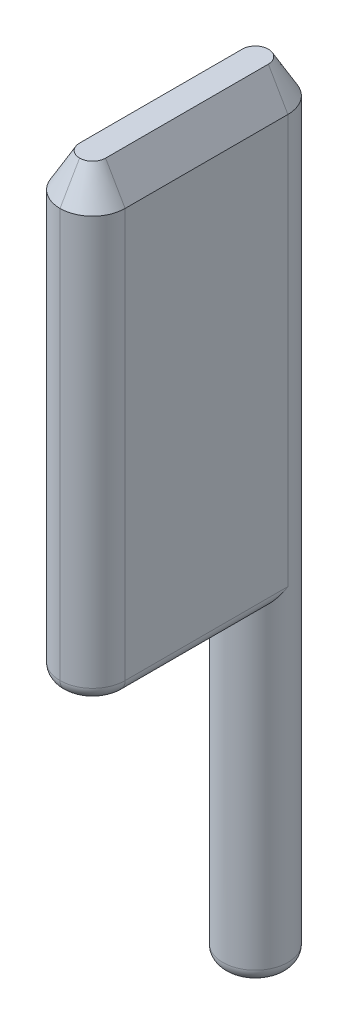
SolidWorks part; units mm, degrees
ref_plane "Front Plane" through (0, 0, 0) normal (0, 0, 1) x (1, 0, 0)
ref_plane "Top Plane" through (0, 0, 0) normal (0, 1, 0) x (1, 0, 0)
ref_plane "Right Plane" through (0, 0, 0) normal (1, 0, 0) x (0, 0, -1)
sketch "Sketch1" plane through (0, 0, 0) normal (0, 1, 0) x (1, 0, 0)
  circle A0 centre (0, 0) radius 5
  dimension "D1" = 10
extrude "Boss-Extrude1" add sketch "Sketch1" along normal blind 50
sketch "Sketch2" plane through (0, 50, 0) normal (0, 1, 0) x (1, 0, 0)
  line L0 (-5, 0) -> (-5, -30)
  line L1 (-5, -30) -> (5, -30)
  line L2 (5, -30) -> (5, 0)
  circle A0 centre (0, 0) radius 5 construction
  arc A1 (-5, 0) -> (5, 0) centre (0, 0) cw
  dimension "D2" = 5
  dimension "30" = 30
extrude "Boss-Extrude2" add sketch "Sketch2" along normal blind 70
fillet "Fillet1" radius 5 2 edges at (-5, 85, 30) (5, 85, 30)
fillet "Fillet2" radius 2 4 edges at (-5, 50, 12.5) (-3.5355, 50, 28.5355) (3.5355, 50, 28.5355) (5, 50, 12.5)
fillet "Fillet3" radius 2 1 edges at (0, 0, 5)
chamfer "Chamfer1" distance 3 angle 60 5 edges at (-3.5355, 120, 28.5355) (-5, 120, 12.5) (3.5355, 120, 28.5355) (0, 120, -5) (5, 120, 12.5) first distance on face at (0, 120, 15.4142)
